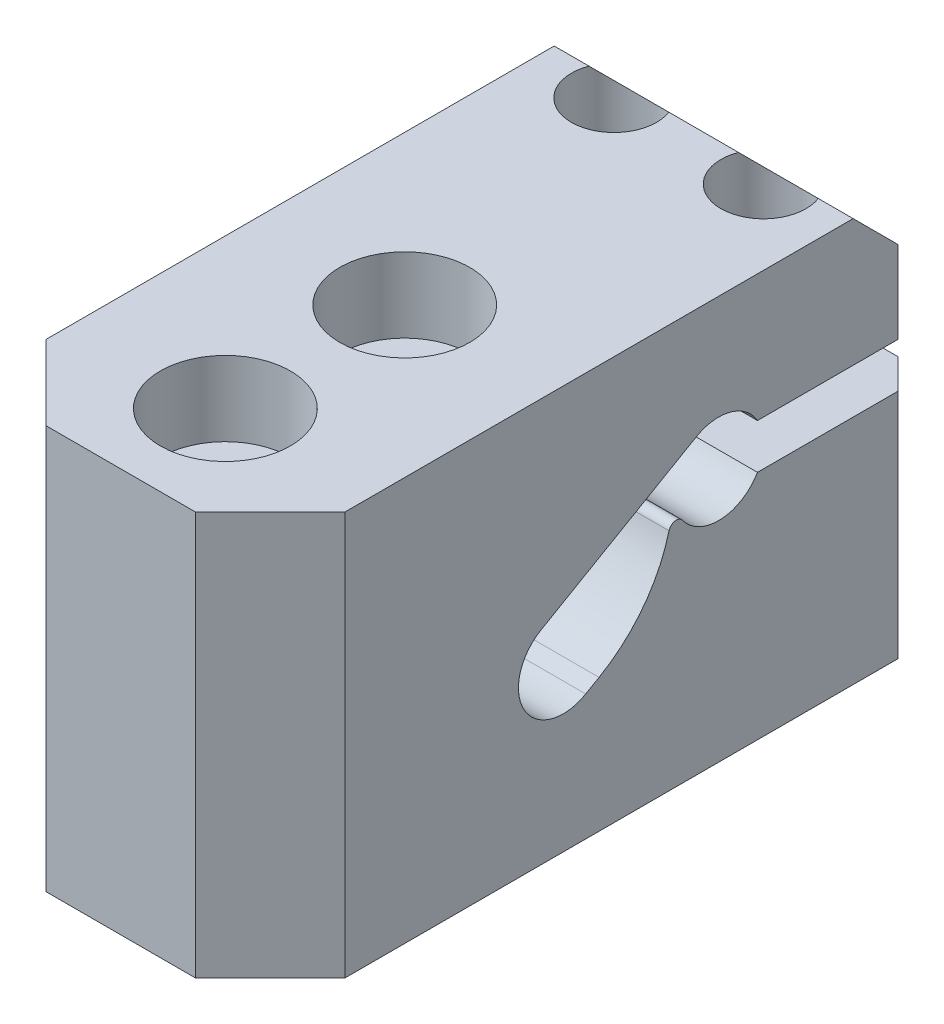
SolidWorks part; units mm, degrees
ref_plane "정면" through (0, 0, 0) normal (0, 0, 1) x (1, 0, 0)
ref_plane "윗면" through (0, 0, 0) normal (0, 1, 0) x (1, 0, 0)
ref_plane "우측면" through (0, 0, 0) normal (1, 0, 0) x (0, 0, -1)
sketch "스케치1" plane through (0, 0, 0) normal (1, 0, 0) x (0, 0, -1)
  line L0 (0, 0) -> (0, -17) construction
  line L1 (-11.8923, -3.4019) -> (-8.8923, -8.5981)
  line L2 (14, -17) -> (-30, -17)
  line L3 (14, -17) -> (14, 5)
  line L4 (9, 10) -> (-30, 10)
  line L5 (-30, -17) -> (-30, 10)
  line L6 (-11.8923, -3.4019) -> (-1.5, 2.5981)
  line L7 (-8.8923, -8.5981) -> (1.5, -2.5981)
  line L8 (-1.5, 2.5981) -> (1.5, -2.5981)
  line L9 (14, 5) -> (9, 10)
  line L10 (0, 0) -> (14, 0) construction
  line L11 (14, 1.5) -> (1, 1.5)
  line L12 (14, 1.5) -> (14, -1.5)
  line L13 (14, -1.5) -> (1, -1.5)
  line L14 (1, 1.5) -> (1, -1.5)
  line L15 (-3, 0) -> (-3.6276, -5.5585)
  circle A0 centre (0, 0) radius 3
  arc A1 (-11.8923, -3.4019) -> (-8.8923, -8.5981) centre (-10.3923, -6) ccw
  point P6 (14, 10)
  dimension "D1" = 6
  dimension "D2" = 17
  dimension "D3" = 10
  dimension "D4" = 6
  dimension "D5" = 30
  dimension "D6" = 14
  dimension "D7" = 12
  dimension "D9" = 3
  dimension "D10" = 13
  dimension "D11" = 44
extrude "보스-돌출1" add sketch "스케치1" along normal blind 20 contours A1 L6 A0 L11 L3 L9 L4 L5 L2 L13 L7 | A0 L15 L7 region at (0, -7.7581, 13.4375) region at (0, -3.348, 2.1714)
fillet "필렛1" radius 10 1 edges at (10, -5.5585, 3.6276)
fillet "필렛2" radius 0.5 1 edges at (10, 0, 3)
sketch "스케치2" plane through (0, 10, 0) normal (0, 1, 0) x (1, 0, 0)
  line L0 (10, 14) -> (10, -30) construction
  line L1 (20, 14) -> (0, 14) construction
  line L2 (20, -30) -> (0, -30) construction
  circle A0 centre (10, -23) radius 4.35
  circle A1 centre (10, -11) radius 4.35
  circle A3 centre (5, 8) radius 1.5
  circle A4 centre (15, 8) radius 1.5
  circle A5 centre (5, 8) radius 2.85
  circle A6 centre (15, 8) radius 2.85
  circle A7 centre (10, -11) radius 2.5
  circle A8 centre (10, -23) radius 2.5
  line M11 (20, 9) -> (0, 9)
  dimension "D1" = 3
  dimension "D4" = 5.7
  dimension "D5" = 8.7
  dimension "D6" = 5
  dimension "D2" = 6
  dimension "D3" = 5
  dimension "D7" = 12
  dimension "D8" = 7
extrude "컷-돌출1" cut sketch "스케치2" against normal blind 5 contours L0 A1 A7 | A1 L0 A7 | A0 L0 A8 | L0 A0 A8 region at (13.0071, 10, 7.9929) region at (13.0071, 10, 19.9929) region at (9.9027, 10, 19.575) region at (9.9027, 10, 7.575)
extrude "컷-돌출2" cut sketch "스케치2<3>" against normal blind 5 contours A6 A4 M11 | A6 A4 M11 | A5 A3 M11 | A5 A3 M11 region at (6.4655, 10, -8.5598) region at (5, 10, -9.8334) region at (15, 10, -9.8334) region at (13.1066, 10, -8.9312)
sketch "스케치2<3>" plane through (0, 10, 0) normal (0, 1, 0) x (1, 0, 0) same geometry as "스케치2"
extrude "컷-돌출3" cut sketch "스케치2<4>" against normal through all contours A4 M11 | A4 M11 | A3 M11 | A3 M11 | L0 A7 | A7 L0 | A8 L0 | L0 A8 region at (11.061, 10, 11) region at (8.939, 10, 11) region at (15, 10, -7.852) region at (15, 10, -9.2032) region at (5, 10, -9.2032) region at (5, 10, -7.852) region at (11.061, 10, 23) region at (8.939, 10, 23)
sketch "스케치2<4>" plane through (0, 10, 0) normal (0, 1, 0) x (1, 0, 0) same geometry as "스케치2"
chamfer "모따기1" distance 5 angle 45 2 edges at (20, -3.5, 30) (0, -3.5, 30)
chamfer "모따기2" distance 2 angle 45 4 edges at (0, -9.25, -14) (0, 3.25, -14) (20, 3.25, -14) (20, -9.25, -14)
